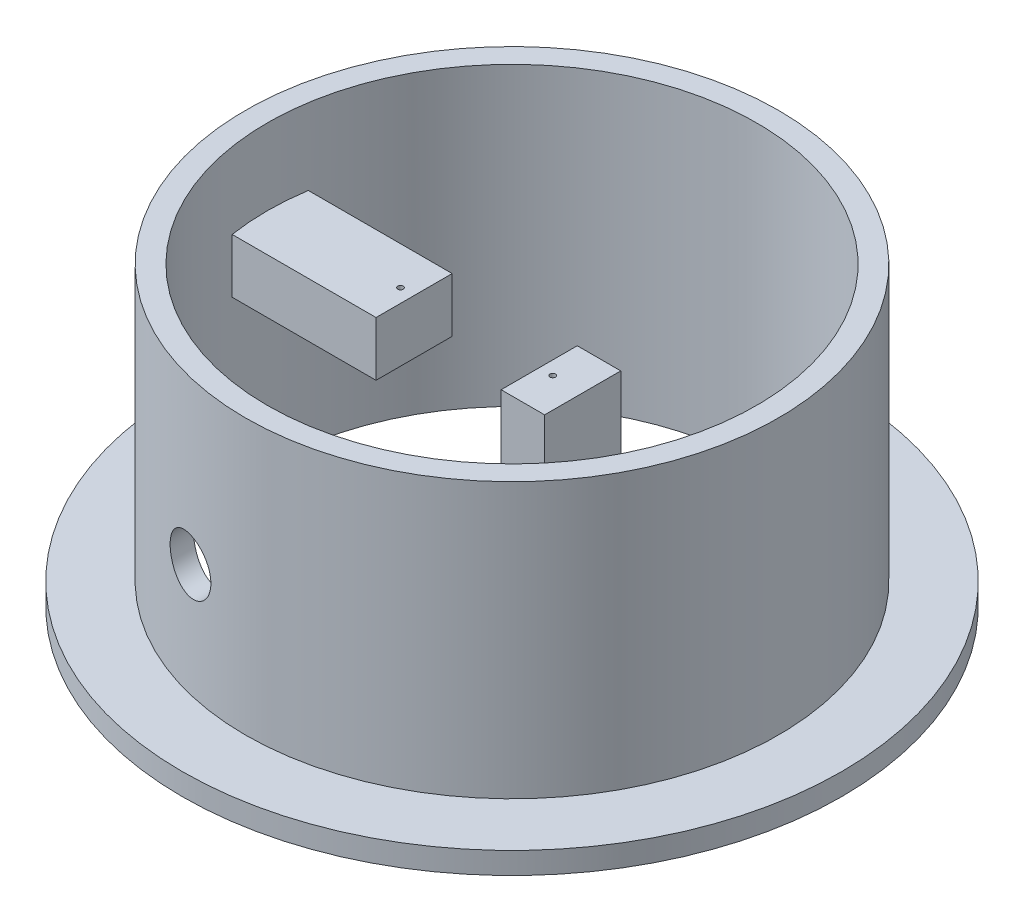
SolidWorks part; units mm, degrees
ref_plane "Front Plane" through (0, 0, 0) normal (0, 0, 1) x (1, 0, 0)
ref_plane "Top Plane" through (0, 0, 0) normal (0, 1, 0) x (1, 0, 0)
ref_plane "Right Plane" through (0, 0, 0) normal (1, 0, 0) x (0, 0, -1)
sketch "Sketch1" plane through (0, 0, 0) normal (0, 1, 0) x (1, 0, 0)
  circle A0 centre (0, 0) radius 60.625
  circle A1 centre (0, 0) radius 45
  dimension "D1" = 121.25
  dimension "D2" = 90
extrude "Boss-Extrude1" add sketch "Sketch1" along normal blind 4
sketch "Sketch2" plane through (0, 4, 0) normal (0, 1, 0) x (1, 0, 0)
  circle A0 centre (0, 0) radius 45 construction
  circle A1 centre (0, 0) radius 45
  circle A2 centre (0, 0) radius 49
  dimension "D1" = 4
extrude "Boss-Extrude2" add sketch "Sketch2" along normal blind 50.5
ref_plane "Plane1" through (0, 34.5, 0) normal (0, 1, 0) x (1, 0, 0)
sketch "Sketch4" plane through (0, 0, 0) normal (0, 0, 1) x (1, 0, 0)
  line L0 (-60.625, 0) -> (60.625, 0) construction
  line L1 (5, 40.5) -> (13, 40.5)
  line L2 (5, 40.5) -> (5, 0)
  line L3 (5, 0) -> (13, 0)
  line L4 (13, 40.5) -> (13, 0)
  line L5 (49, 54.5) -> (-49, 54.5) construction
  line L6 (-45, 54.5) -> (-45, 4)
  line L7 (-18, 40.5) -> (-45, 40.5)
  line L8 (-18, 40.5) -> (-18, 30.5)
  line L9 (-18, 30.5) -> (-45, 30.5)
  line L10 (-45, 40.5) -> (-45, 30.5)
  line L11 (60.625, 4) -> (-60.625, 4) construction
  line L12 (-18, 30.5) -> (-45, 3.5)
  dimension "D1" = 5
  dimension "D2" = 8
  dimension "D3" = 14
  dimension "D4" = 23
  dimension "D5" = 27
  dimension "D6" = 10
  dimension "D7" = 45
  dimension "D8" = 14
extrude "Boss-Extrude4" add sketch "Sketch4" along normal mid plane 14 contours L9 L8 L7 L6 | L12 L9 L6 | L1 L4 L3 L2 region at (-31.5, 35.5, 0)
sketch "Sketch5" plane through (0, 0, 0.8324) normal (0, -1, 0) x (1, 0, 0)
  line L0 (0.9227, 14.5796) -> (36.1058, 30.1379)
  line L1 (0.9227, -16.0291) -> (36.6512, -32.9046)
  line L2 (0.9227, 14.5796) -> (0.9227, -16.0291)
  arc A1 (36.6512, -32.9046) -> (36.1058, 30.1379) centre (-2.8733, -1.7229) ccw
extrude "Boss-Extrude5" add sketch "Sketch5" against normal up to surface (4 mm away) contours L0 A1 L1 L2 up to face at (0, 4, 60.625)
sketch "Sketch6" plane through (0, 0, 0) normal (0, 0, 1) x (1, 0, 0)
  circle A0 centre (-11.8474, 24.4856) radius 5
extrude "Cut-Extrude2" cut sketch "Sketch6" along normal blind 52 contours A0
sketch "Sketch11" plane through (0, 4, 0) normal (0, 1, 0) x (1, 0, 0)
  line L0 (16.2655, 12.7324) -> (16.2655, -6.5497)
  line L1 (16.2655, -6.5497) -> (5.715, -6.5497)
  line L2 (5.715, -6.5497) -> (5.715, -11.643)
  line L3 (5.715, -11.643) -> (30.818, -22.5574)
  line L4 (16.2655, 12.7324) -> (32.152, 20.615)
  arc A0 (32.152, 20.615) -> (30.818, -22.5574) centre (5.8984, -0.1806) cw
extrude "Cut-Extrude6" cut sketch "Sketch11" against normal through all
sketch "Sketch14" plane through (0, 54.5, 0) normal (0, 1, 0) x (1, 0, 0)
  line L0 (0, 45) -> (0, -65.3775) construction
  line L1 (-49, 0) -> (78.814, 0) construction
  circle A0 centre (0, 0) radius 45 construction
  circle A1 centre (0, 0) radius 49 construction
  circle A2 centre (0, 0) radius 49 construction
sketch "Sketch15" plane through (0, 40.5, 0) normal (0, 1, 0) x (1, 0, 0)
  line L2 (-49, 0) -> (78.814, 0) construction
  line L3 (-18, -7) -> (-18, 7) construction
  line L4 (5, -7) -> (5, 7) construction
  circle A2 centre (-20.5, 0) radius 0.5
  circle A3 centre (7.5, 0) radius 0.5
  dimension "D1" = 1
  dimension "D2" = 1
  dimension "D3" = 2.5
  dimension "D4" = 2.5
extrude "Cut-Extrude7" cut sketch "Sketch15" against normal blind 4.5
